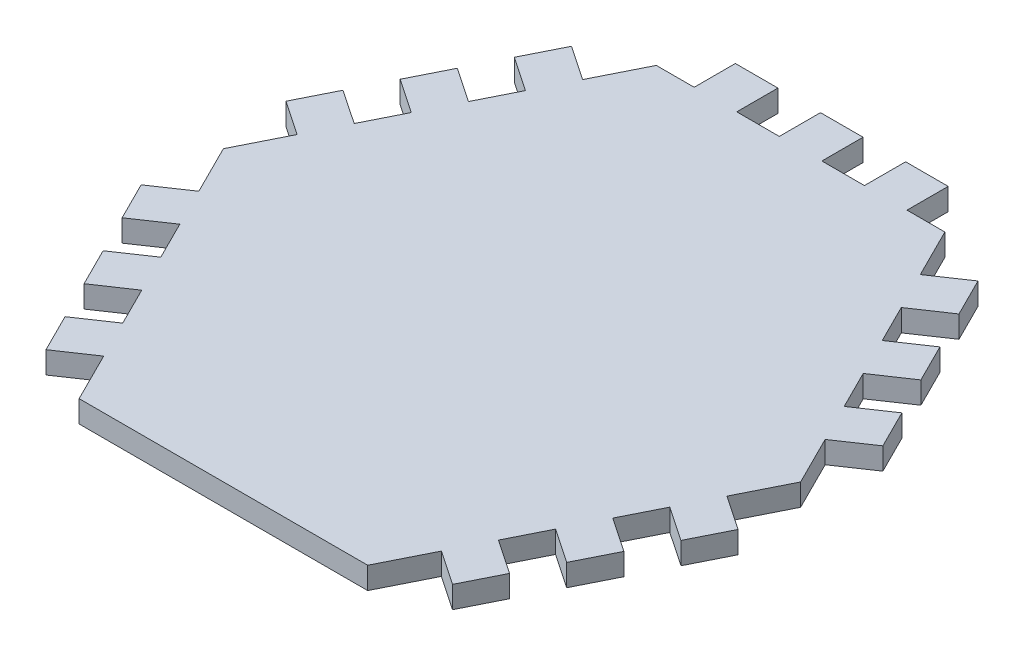
SolidWorks part; units mm, degrees
ref_plane "Front Plane" through (0, 0, 0) normal (0, 0, 1) x (1, 0, 0)
ref_plane "Top Plane" through (0, 0, 0) normal (0, 1, 0) x (1, 0, 0)
ref_plane "Right Plane" through (0, 0, 0) normal (1, 0, 0) x (0, 0, -1)
sketch "Sketch1" plane through (0, 0, 0) normal (0, 1, 0) x (1, 0, 0)
  line L0 (-36.6703, -35.293) -> (5.3697, -35.293) construction
  line L1 (5.3697, -35.293) -> (26.3947, 6.7497) construction
  line L2 (26.3947, 6.7497) -> (5.3697, 48.7923) construction
  line L3 (5.3697, 48.7923) -> (-36.6703, 48.7923) construction
  line L4 (-36.6703, 48.7923) -> (-57.6953, 6.7497) construction
  line L5 (-57.6953, 6.7497) -> (-36.6703, -35.293) construction
  line L9 (112.1005, -40.6411) -> (184.9205, -40.6411) construction
  line L10 (184.9205, -40.6411) -> (184.9205, 1.4015) construction
  line L11 (184.9205, 1.4015) -> (112.1005, -40.6411) construction
  line L12 (5.3697, -35.293) -> (8.9479, -28.1378)
  line L15 (13.961, -31.528) -> (8.9479, -28.1378)
  line L17 (11.7216, -22.5914) -> (16.7347, -25.9815)
  line L19 (19.5084, -20.435) -> (14.4953, -17.0449)
  line L21 (17.2691, -11.4984) -> (22.2821, -14.8886)
  line L23 (25.0558, -9.3421) -> (20.0428, -5.952)
  line L25 (22.8165, -0.4055) -> (27.8296, -3.7957)
  line L27 (27.8296, 17.295) -> (22.8165, 13.9048)
  line L29 (20.0428, 19.4513) -> (25.0558, 22.8414)
  line L31 (22.2821, 28.3879) -> (17.2691, 24.9978)
  line L33 (14.4953, 30.5442) -> (19.5084, 33.9344)
  line L35 (16.7347, 39.4808) -> (11.7216, 36.0907)
  line L37 (8.9479, 41.6371) -> (13.961, 45.0273)
  line L40 (-0.1469, 54.7923) -> (-0.1469, 48.7923)
  line L42 (-6.3483, 48.7923) -> (-6.3483, 54.7923)
  line L44 (-12.5496, 54.7923) -> (-12.5496, 48.7923)
  line L46 (-18.751, 48.7923) -> (-18.751, 54.7923)
  line L48 (-24.9523, 54.7923) -> (-24.9523, 48.7923)
  line L50 (-31.1537, 48.7923) -> (-31.1537, 54.7923)
  line L53 (-45.2616, 45.0273) -> (-40.2485, 41.6371)
  line L55 (-43.0222, 36.0907) -> (-48.0353, 39.4808)
  line L57 (-50.809, 33.9344) -> (-45.7959, 30.5442)
  line L59 (-48.5697, 24.9978) -> (-53.5827, 28.3879)
  line L61 (-56.3564, 22.8414) -> (-51.3434, 19.4513)
  line L63 (-54.1171, 13.9048) -> (-59.1302, 17.295)
  line L66 (-59.1302, -3.7957) -> (-54.1171, -0.4055)
  line L68 (-51.3434, -5.952) -> (-56.3564, -9.3421)
  line L70 (-53.5827, -14.8886) -> (-48.5697, -11.4984)
  line L72 (-45.7959, -17.0449) -> (-50.809, -20.435)
  line L74 (-48.0353, -25.9815) -> (-43.0222, -22.5914)
  line L76 (-40.2485, -28.1378) -> (-45.2616, -31.528)
  line L79 (13.961, -31.528) -> (16.7347, -25.9815)
  line L80 (19.5084, -20.435) -> (22.2821, -14.8886)
  line L81 (11.7216, -22.5914) -> (14.4953, -17.0449)
  line L82 (17.2691, -11.4984) -> (20.0428, -5.952)
  line L83 (25.0558, -9.3421) -> (27.8296, -3.7957)
  line L84 (22.8165, -0.4055) -> (26.3947, 6.7497)
  line L85 (26.3947, 6.7497) -> (22.8165, 13.9048)
  line L86 (27.8296, 17.295) -> (25.0558, 22.8414)
  line L87 (20.0428, 19.4513) -> (17.2691, 24.9978)
  line L88 (22.2821, 28.3879) -> (19.5084, 33.9344)
  line L89 (14.4953, 30.5442) -> (11.7216, 36.0907)
  line L90 (16.7347, 39.4808) -> (13.961, 45.0273)
  line L91 (8.9479, 41.6371) -> (5.3697, 48.7923)
  line L92 (5.3697, 48.7923) -> (-0.1469, 48.7923)
  line L93 (-0.1469, 54.7923) -> (-6.3483, 54.7923)
  line L94 (-6.3483, 48.7923) -> (-12.5496, 48.7923)
  line L95 (-12.5496, 54.7923) -> (-18.751, 54.7923)
  line L96 (-24.9523, 48.7923) -> (-18.751, 48.7923)
  line L97 (-24.9523, 54.7923) -> (-31.1537, 54.7923)
  line L98 (-31.1537, 48.7923) -> (-36.6703, 48.7923)
  line L99 (-36.6703, 48.7923) -> (-40.2485, 41.6371)
  line L100 (-45.2616, 45.0273) -> (-48.0353, 39.4808)
  line L101 (-43.0222, 36.0907) -> (-45.7959, 30.5442)
  line L102 (-50.809, 33.9344) -> (-53.5827, 28.3879)
  line L103 (-48.5697, 24.9978) -> (-51.3434, 19.4513)
  line L104 (-56.3564, 22.8414) -> (-59.1302, 17.295)
  line L105 (-54.1171, 13.9048) -> (-57.6953, 6.7497)
  line L106 (-57.6953, 6.7497) -> (-54.1171, -0.4055)
  line L107 (-59.1302, -3.7957) -> (-56.3564, -9.3421)
  line L108 (-51.3434, -5.952) -> (-48.5697, -11.4984)
  line L109 (-53.5827, -14.8886) -> (-50.809, -20.435)
  line L110 (-45.7959, -17.0449) -> (-43.0222, -22.5914)
  line L111 (-48.0353, -25.9815) -> (-45.2616, -31.528)
  line L112 (-40.2485, -28.1378) -> (-36.6703, -35.293)
  line L113 (-36.6703, -35.293) -> (5.3697, -35.293)
  point P7 (0, 0)
  point P24 (0, 0)
  point P36 (0, 0)
  point P48 (0, 0)
  point P61 (0, 0)
  point P74 (0, 0)
  point P75 (0, 0)
  point P76 (0, 0)
  point P77 (0, 0)
  point P78 (26.4427, 20.0682)
  point P79 (0, 0)
  dimension "D1" = 42.04
  dimension "D6" = 72.82
  dimension "D7" = 30
  dimension "D8" = 84.0853
  dimension "D9" = 42.0426
  dimension "D10" = 84.0853
  dimension "D3" = 84.09
  dimension "D11" = 6.2014
  dimension "D2" = 6
  dimension "D4" = 6
  dimension "D5" = 6
  dimension "D12" = 6
  dimension "D13" = 6
  dimension "D15" = 82.5
  dimension "D16" = 82.5
  dimension "D17" = 82.5
  dimension "D18" = 82.5
  dimension "D14" = 8
extrude "Boss-Extrude1" add sketch "Sketch1" along normal blind 3.2
equation "\"thick\"=6"
equation "\"D10@Sketch1\"=\"D8@Sketch1\""
equation "\"D3@Sketch1\"=84.09"
equation "\"D2@Sketch1\"=\"thick\""
equation "\"D4@Sketch1\"=\"thick\""
equation "\"D5@Sketch1\"=\"thick\""
equation "\"D12@Sketch1\"=\"thick\""
equation "\"D13@Sketch1\"=\"thick\""
